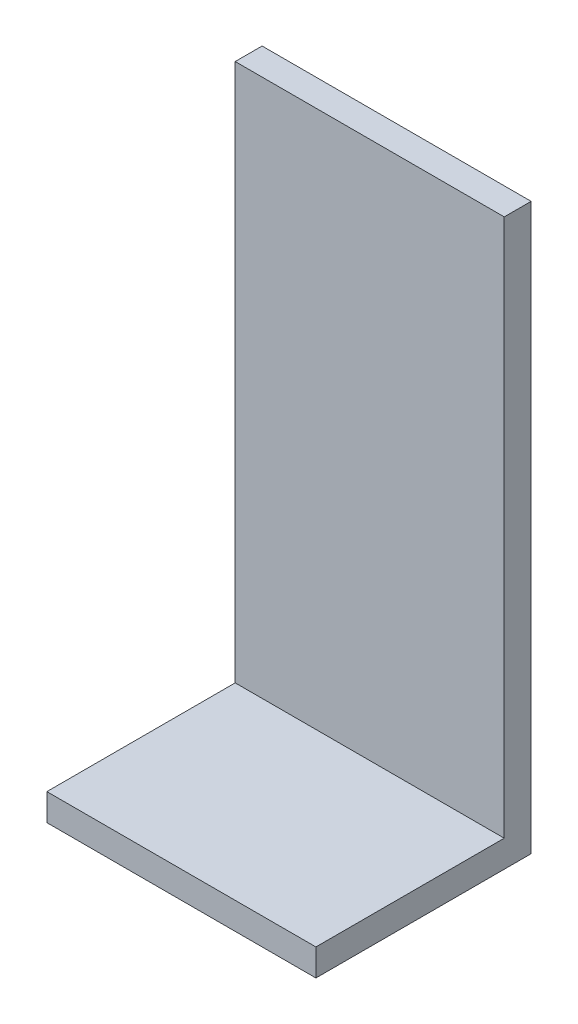
SolidWorks part; units mm, degrees
ref_plane "Front Plane" through (0, 0, 0) normal (0, 0, 1) x (1, 0, 0)
ref_plane "Top Plane" through (0, 0, 0) normal (0, 1, 0) x (1, 0, 0)
ref_plane "Right Plane" through (0, 0, 0) normal (1, 0, 0) x (0, 0, -1)
sketch "Sketch1" plane through (0, 0, 0) normal (0, 0, 1) x (1, 0, 0)
  line L1 (0, 0) -> (31.75, 0)
  line L2 (0, 0) -> (0, 63.5)
  line L3 (0, 63.5) -> (31.75, 63.5)
  line L4 (31.75, 0) -> (31.75, 63.5)
  line L5 (0, 0) -> (31.75, 0)
  line L6 (0, 0) -> (0, -3.175)
  line L7 (0, -3.175) -> (31.75, -3.175)
  line L8 (31.75, 0) -> (31.75, -3.175)
  point P9 (0, 0)
  dimension "D1" = 31.75
  dimension "D2" = 3.175
  dimension "D3" = 63.5
extrude "Boss-Extrude1" add sketch "Sketch1" along normal blind 3.175 contours L1 L4 L3 L2 region at (15.875, 31.75, 0)
extrude "Boss-Extrude2" add sketch "Sketch1<3>" along normal blind 25.4 contours L8 L1 L6 L7 region at (15.875, -1.5875, 0)
sketch "Sketch1<3>" plane through (0, 0, 0) normal (0, 0, 1) x (1, 0, 0) same geometry as "Sketch1"
